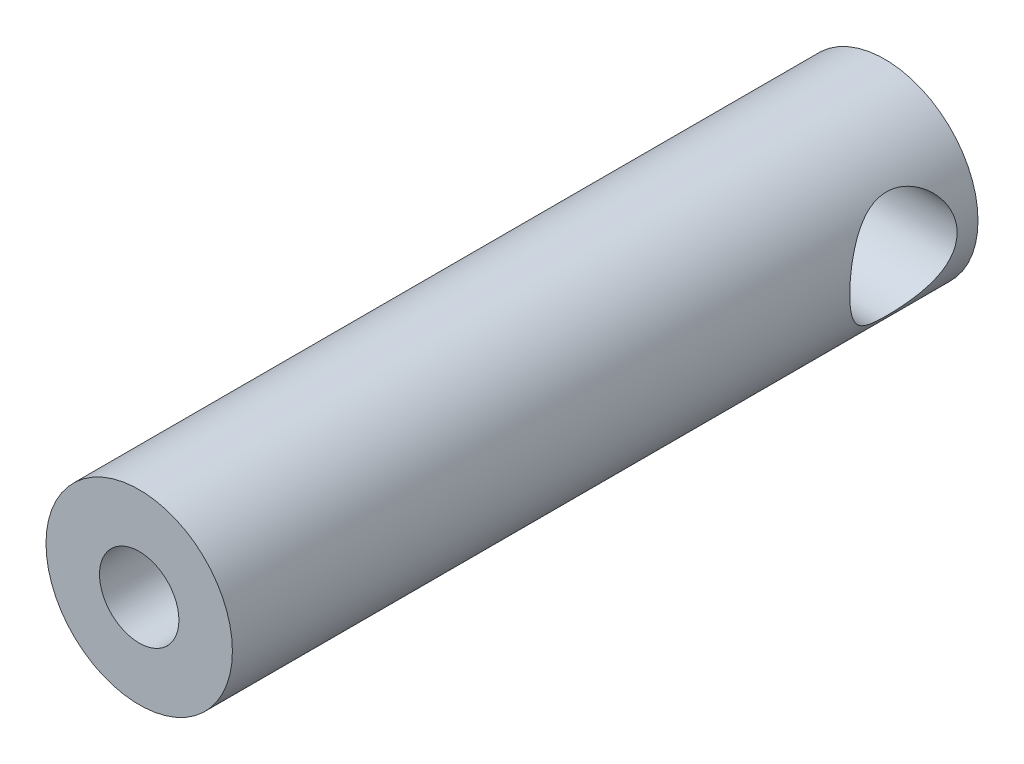
SolidWorks part; units mm, degrees
ref_plane "Front Plane" through (0, 0, 0) normal (0, 0, 1) x (1, 0, 0)
ref_plane "Top Plane" through (0, 0, 0) normal (0, 1, 0) x (1, 0, 0)
ref_plane "Right Plane" through (0, 0, 0) normal (1, 0, 0) x (0, 0, -1)
sketch "Sketch1" plane through (0, 0, 0) normal (0, 0, 1) x (1, 0, 0)
  circle A0 centre (0, 0) radius 3.175
  dimension "D1" = 6.35
extrude "Boss-Extrude1" add sketch "Sketch1" along normal blind 25.4
sketch "Sketch2" plane through (0, 0, 25.4) normal (0, 0, 1) x (1, 0, 0)
  circle A0 centre (0, 0) radius 1.905
  dimension "D1" = 3.81
extrude "Cut-Extrude1" [suppressed] cut sketch "Sketch2" against normal blind 12.7
sketch "Sketch3" plane through (0, 0, 0) normal (1, 0, 0) x (0, 0, -1)
  circle A0 centre (-2.54, 0) radius 1.8288
  dimension "D2" = 3.6576
  dimension "D1" = 2.54
extrude "Cut-Extrude2" cut sketch "Sketch3" against normal through all and the other way through all
hole_wizard "#6-32 Tapped Hole1" positions "Sketch5" profile "Sketch6" tap size "#6-32" standard "ANSI Inch"
sketch "Sketch5" plane through (0, 0, 25.4) normal (0, 0, 1) x (1, 0, 0)
  point P0 (0, 0)
sketch "Sketch6" plane through (0, 0, 25.4) normal (1, 0, 0) x (0, -1, 0)
  line L0 (0, 0) -> (0, 13.5127)
  line L1 (0, 13.5127) -> (1.3525, 12.7)
  line L2 (1.3525, 12.7) -> (1.3525, 0)
  line L5 (1.3525, 0) -> (0, 0)
  line L10 (0, 13.5127) -> (-1.3526, 12.7) construction
  line L11 (0, -6.35) -> (0, 107.95) construction
  dimension "Tap Drill Dia." = 2.7051
  dimension "Tap Drill Depth" = 12.7
  dimension "Drill Angle" = 118
cosmetic thread "Hole Thread1" parameters "D1"=1.0644, "D2"=3.5052
